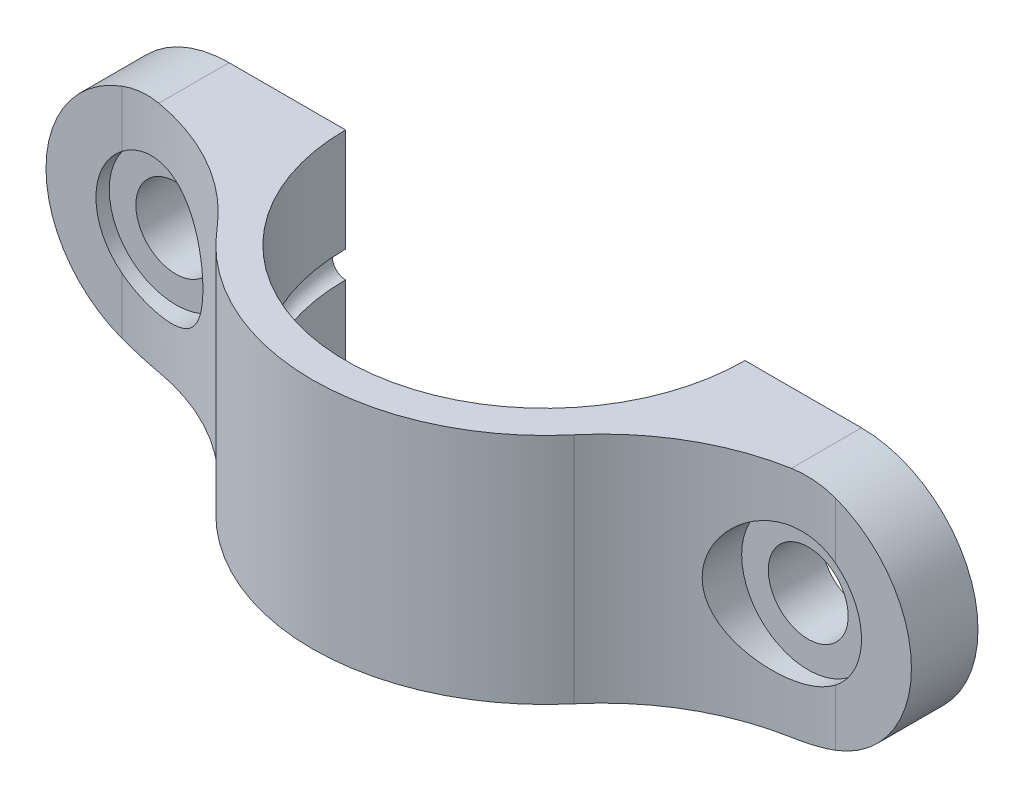
SolidWorks part; units mm, degrees
ref_plane "Front Plane" through (0, 0, 0) normal (0, 0, 1) x (1, 0, 0)
ref_plane "Top Plane" through (0, 0, 0) normal (0, 1, 0) x (1, 0, 0)
ref_plane "Right Plane" through (0, 0, 0) normal (1, 0, 0) x (0, 0, -1)
sketch "Sketch1" plane through (0, 0, 0) normal (0, 1, 0) x (1, 0, 0)
  line L0 (-30, 0) -> (30, 0) construction
  line L1 (30, 0) -> (65, 0)
  line L2 (0, 0) -> (0, -30) construction
  line L3 (-30, 0) -> (-65, 0)
  line L4 (53.619, -10) -> (65, -10)
  line L5 (-53.619, -10) -> (-65, -10)
  line L6 (-30, -10) -> (-65, -10) construction
  line L7 (30, -10) -> (65, -10) construction
  line L8 (-65, 0) -> (-65, -10)
  line L9 (65, 0) -> (65, -10)
  arc A0 (-30, 0) -> (30, 0) centre (0, 0) ccw
  arc A1 (-26.8095, -22.5) -> (26.8095, -22.5) centre (0, 0) ccw
  arc A2 (-35, 0) -> (35, 0) centre (0, 0) ccw construction
  arc A3 (53.619, -10) -> (26.8095, -22.5) centre (53.619, -45) ccw
  arc A4 (-26.8095, -22.5) -> (-53.619, -10) centre (-53.619, -45) ccw
  point P4 (0, 0)
  dimension "D4" = 30
  dimension "D6" = 35
  dimension "D5" = 35
  dimension "D1" = 5
  dimension "D2" = 10
  dimension "D3" = 10
extrude "Boss-Extrude1" add sketch "Sketch1" along normal mid plane 35
sketch "Sketch2" plane through (0, 0, 0) normal (0, 0, -1) x (-1, 0, 0)
  circle A0 centre (47.5, 0) radius 6
  circle A1 centre (-47.5, 0) radius 6
  dimension "D1" = 12
  dimension "D2" = 12
extrude "Cut-Extrude1" cut sketch "Sketch2" against normal blind 35
sketch "Sketch3" plane through (0, 0, 0) normal (0, 0, -1) x (-1, 0, 0)
  line L0 (30, 17.5) -> (30, -17.5) construction
  circle A0 centre (30, 0) radius 2
  dimension "D1" = 4
revolve "Cut-Revolve1" cut sketch "Sketch3" angle 360 about axis through (0, 17.5, 0) along (0, -1, 0)
fillet "Fillet1" 2 edges at (65, -17.5, 5) (65, 17.5, 5) type full round first side face at (0, -17.5, 12.1557) second side face at (0, 17.5, 12.1557) middle face at (65, 0, 5)
fillet "Fillet2" 2 edges at (-65, 17.5, 5) (-65, -17.5, 5) type full round first side face at (-9.8096, 17.5, 12.583) second side face at (-9.8096, -17.5, 12.583) middle face at (-65, 0, 5)
sketch "Sketch4" plane through (0, 0, 0) normal (0, 0, -1) x (-1, 0, 0)
  circle A0 centre (-47.5, 0) radius 10
  circle A1 centre (47.5, 0) radius 10
  dimension "D1" = 20
  dimension "D2" = 20
extrude "Cut-Extrude2" cut sketch "Sketch4" against normal blind 35 from offset 8 offset against normal yes
